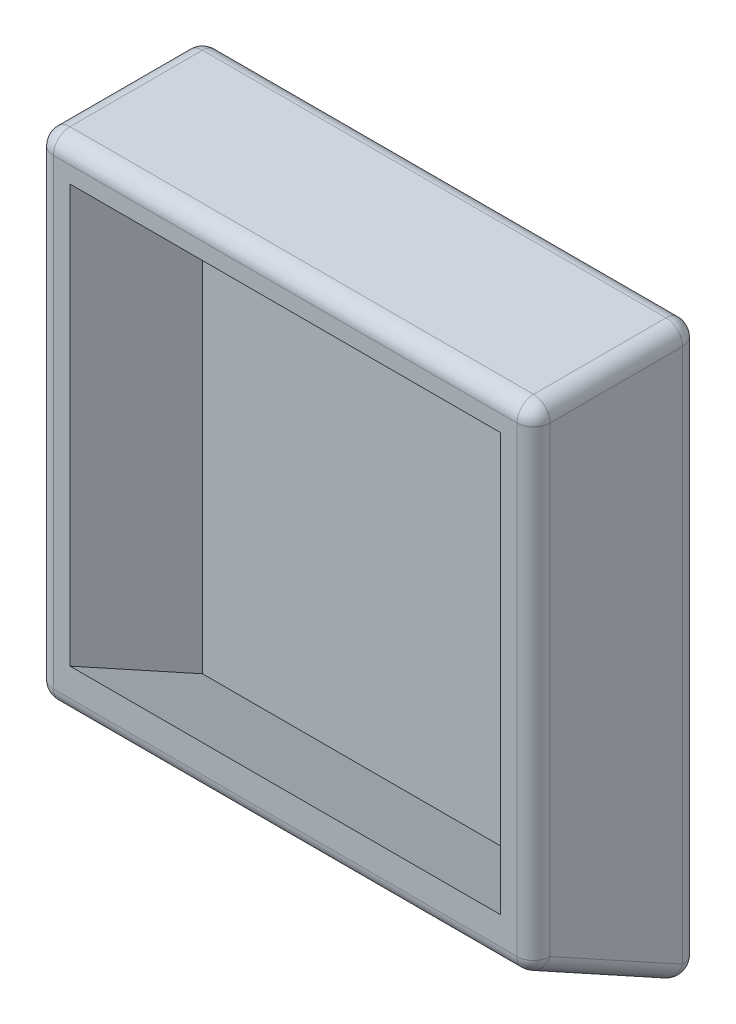
SolidWorks part; units mm, degrees
ref_plane "Front Plane" through (0, 0, 0) normal (0, 0, 1) x (1, 0, 0)
ref_plane "Top Plane" through (0, 0, 0) normal (0, 1, 0) x (1, 0, 0)
ref_plane "Right Plane" through (0, 0, 0) normal (1, 0, 0) x (0, 0, -1)
sketch "Sketch1" plane through (0, 0, 0) normal (0, 0, 1) x (1, 0, 0)
  line L0 (-150, 175) -> (-150, -175)
  line L1 (-150, -175) -> (150, -175)
  line L2 (150, -175) -> (150, 175)
  line L3 (150, 175) -> (-150, 175)
  dimension "D1" = 150
  dimension "D2" = 300
  dimension "D3" = 350
  dimension "D4" = 175
extrude "Boss-Extrude1" add sketch "Sketch1" along normal blind 100
sketch "Sketch2" plane through (-150, 0, 0) normal (-1, 0, 0) x (0, 0, 1)
  line L0 (0, -175) -> (100, -120)
  line L1 (100, 175) -> (100, -175) construction
  line L2 (100, -120) -> (100, -175)
  line L3 (100, -175) -> (0, -175)
  dimension "D1" = 55
extrude "Cut-Extrude1" cut sketch "Sketch2" against normal through all
fillet "Fillet1" radius 10 12 edges at (-150, 27.5, 100) (0, 175, 100) (150, 27.5, 100) (0, -120, 100) (-150, 0, 0) (0, -175, 0) (150, 0, 0) (0, 175, 0) (150, 175, 50) (-150, 175, 50) (-150, -147.5, 50) (150, -147.5, 50)
shell "Shell1" thickness 20 removed face at (0, 25.4564, 100)
